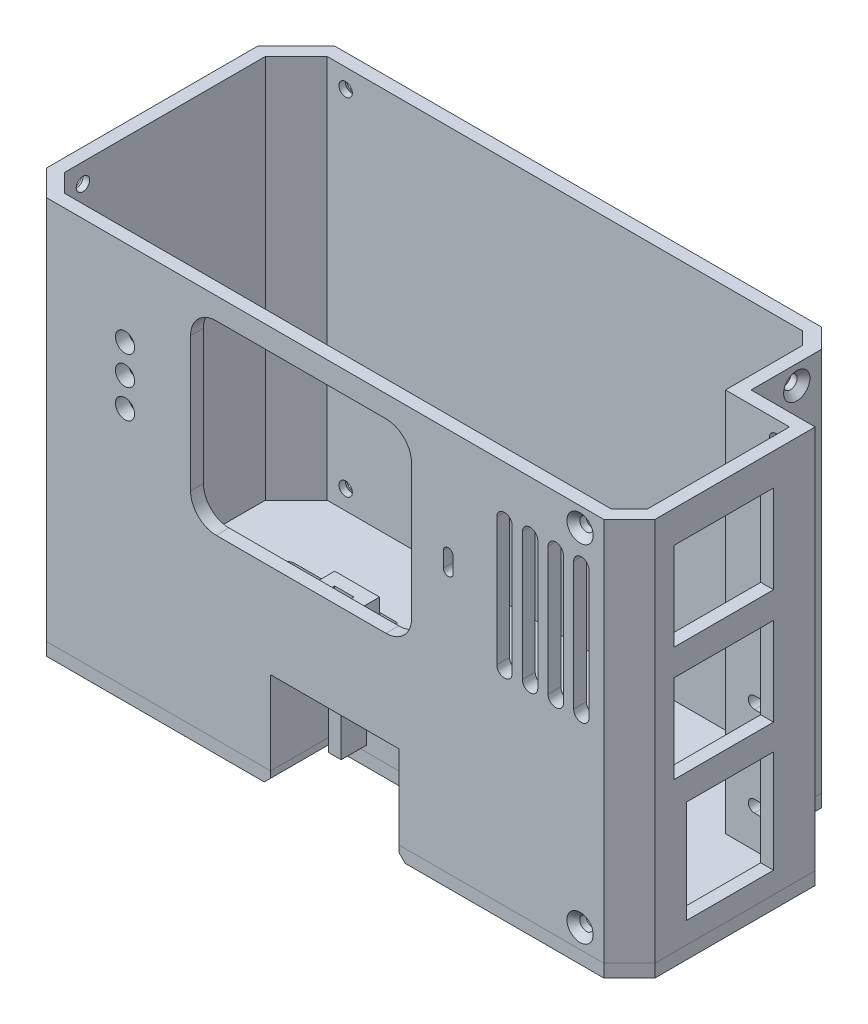
SolidWorks part; units mm, degrees
ref_plane "前视基准面" through (0, 0, 0) normal (0, 0, 1) x (1, 0, 0)
ref_plane "上视基准面" through (0, 0, 0) normal (0, 1, 0) x (1, 0, 0)
ref_plane "右视基准面" through (0, 0, 0) normal (1, 0, 0) x (0, 0, -1)
other "Configuration Table"
sketch "草图1" plane through (0, 0, 0) normal (0, 0, 1) x (1, 0, 0)
  line L1 (-105.5174, 35.9027) -> (-10.5174, 35.9027)
  line L2 (-105.5174, 35.9027) -> (-105.5174, -26.0973)
  line L3 (-105.5174, -26.0973) -> (-10.5174, -26.0973)
  line L4 (-10.5174, 35.9027) -> (-10.5174, -26.0973)
  dimension "D1" = 62
  dimension "D2" = 95
extrude "凸台-拉伸1" add sketch "草图1" along normal blind 43
sketch "草图4" plane through (0, -26.0973, 0) normal (0, -1, 0) x (1, 0, 0)
  line L0 (-10.5174, 43) -> (-10.5174, 0) construction
  line L1 (-10.5174, 14) -> (-20.5174, 14)
  line L2 (-10.5174, 14) -> (-10.5174, 0)
  line L3 (-10.5174, 0) -> (-20.5174, 0)
  line L4 (-20.5174, 14) -> (-20.5174, 0)
  line L5 (-105.5174, 0) -> (-10.5174, 0) construction
  dimension "D1" = 14
  dimension "D2" = 10
extrude "切除-拉伸3" cut sketch "草图4" against normal up to next
chamfer "倒角2" distance 6 angle 45 1 edges at (-105.5174, 4.9027, 0)
chamfer "倒角3" distance 4 angle 45 2 edges at (-105.5174, 4.9027, 43) (-10.5174, 4.9027, 43)
sketch "草图7" plane through (0, 0, 43) normal (0, 0, 1) x (1, 0, 0)
  line L0 (-101.5174, -26.0973) -> (-14.5174, -26.0973) construction
  line L1 (-46.5174, -26.0973) -> (-66.5174, -26.0973)
  line L2 (-46.5174, -26.0973) -> (-46.5174, -6.0973)
  line L3 (-46.5174, -6.0973) -> (-66.5174, -6.0973)
  line L4 (-66.5174, -26.0973) -> (-66.5174, -6.0973)
  line L6 (-10.5174, -26.0973) -> (-10.5174, 35.9027) construction
  dimension "D1" = 36
  dimension "D2" = 20
  dimension "D3" = 20
extrude "切除-拉伸5" cut sketch "草图7" against normal blind 10
shell "抽壳3" thickness 2 removed face at (-54.2952, 35.9027, 22)
sketch "草图9" plane through (0, -6.0973, 0) normal (0, -1, 0) x (1, 0, 0)
  line L0 (-44.5174, 41) -> (-68.5174, 41) construction
  line L1 (-46.5174, 41) -> (-66.5174, 41)
  line L2 (-46.5174, 41) -> (-46.5174, 33)
  line L3 (-46.5174, 33) -> (-66.5174, 33)
  line L4 (-66.5174, 41) -> (-66.5174, 33)
  line L5 (-66.5174, 33) -> (-46.5174, 33) construction
  line L8 (-66.5174, 33) -> (-66.5174, 43) construction
  line L9 (-46.5174, 33) -> (-46.5174, 43) construction
extrude "切除-拉伸6" cut sketch "草图9" against normal blind 10
sketch "草图10" plane through (0, -6.0973, 0) normal (0, -1, 0) x (1, 0, 0)
  line L4 (-66.5174, 43) -> (-66.5174, 41)
  line L5 (-66.5174, 41) -> (-46.5174, 41)
  line L6 (-46.5174, 41) -> (-46.5174, 43)
  line L7 (-46.5174, 43) -> (-66.5174, 43)
  line L8 (-66.5174, 43) -> (-66.5174, 41)
  line L9 (-66.5174, 41) -> (-46.5174, 41)
  line L10 (-46.5174, 41) -> (-46.5174, 43)
  line L11 (-46.5174, 43) -> (-66.5174, 43)
  dimension "D1" = 0
extrude "凸台-拉伸2" add sketch "草图10" along normal blind 5
sketch "草图11" plane through (0, 0, 43) normal (0, 0, 1) x (1, 0, 0)
  line L0 (-10.5174, 35.9027) -> (-10.5174, -26.0973) construction
  line L1 (-44.5174, 32.5027) -> (-79.0174, 32.5027)
  line L2 (-44.5174, 32.5027) -> (-44.5174, 3.5027)
  line L3 (-44.5174, 3.5027) -> (-79.0174, 3.5027)
  line L4 (-79.0174, 32.5027) -> (-79.0174, 3.5027)
  line L5 (-14.5174, 35.9027) -> (-101.5174, 35.9027) construction
  point P7 (0, 0)
  point P9 (-38.5314, 35.9027)
  dimension "D1" = 34.5
  dimension "D2" = 29
  dimension "D3" = 34
  dimension "D4" = 3.4
extrude "切除-拉伸7" cut sketch "草图11" against normal blind 2
fillet "圆角5" radius 4 4 edges at (-79.0174, 32.5027, 42) (-79.0174, 3.5027, 42) (-44.5174, 32.5027, 42) (-44.5174, 3.5027, 42)
sketch "草图12" plane through (0, 0, 33) normal (0, 0, 1) x (1, 0, 0)
  line L0 (-46.5174, -4.0973) -> (-66.5174, -4.0973) construction
  line L1 (-63.5174, -4.0973) -> (-49.5174, -4.0973)
  line L2 (-63.5174, -4.0973) -> (-63.5174, -23.0973)
  line L3 (-63.5174, -23.0973) -> (-49.5174, -23.0973)
  line L4 (-49.5174, -4.0973) -> (-49.5174, -23.0973)
  line L5 (-66.5174, -4.0973) -> (-66.5174, -11.0973) construction
  line L6 (-46.5174, -4.0973) -> (-46.5174, -11.0973) construction
  line L7 (-66.5174, -26.0973) -> (-46.5174, -26.0973) construction
  dimension "D1" = 3
  dimension "D2" = 3
  dimension "D3" = 3
extrude "凸台-拉伸3" add sketch "草图12" along normal blind 4
sketch "草图13" plane through (0, -4.0973, 0) normal (0, 1, 0) x (1, 0, 0)
  line L0 (-44.5174, -31) -> (-68.5174, -31) construction
  line L1 (-61.5174, -31) -> (-51.5174, -31)
  line L2 (-61.5174, -31) -> (-61.5174, -35.5752)
  line L3 (-61.5174, -35.5752) -> (-51.5174, -35.5752)
  line L4 (-51.5174, -31) -> (-51.5174, -35.5752)
  line L5 (-68.5174, -31) -> (-68.5174, -41) construction
  line L6 (-44.5174, -31) -> (-44.5174, -41) construction
  dimension "D1" = 7
  dimension "D2" = 7
extrude "切除-拉伸8" cut sketch "草图13" against normal blind 17
sketch "草图14" plane through (0, 0, 37) normal (0, 0, 1) x (1, 0, 0)
  line L0 (-63.5174, -23.0973) -> (-49.5174, -23.0973) construction
  line L1 (-61.5174, -4.0973) -> (-51.5174, -4.0973)
  line L2 (-61.5174, -4.0973) -> (-61.5174, -23.0973)
  line L3 (-61.5174, -23.0973) -> (-51.5174, -23.0973)
  line L4 (-51.5174, -4.0973) -> (-51.5174, -23.0973)
extrude "切除-拉伸9" cut sketch "草图14" against normal up to surface (4 mm away) up to face at (-56.5174, -14.3473, 33)
chamfer "倒角4" distance 1 angle 45 2 edges at (-66.5174, -26.0973, 38) (-46.5174, -26.0973, 38)
sketch "草图15" plane through (-10.5174, 0, 0) normal (1, 0, 0) x (0, 0, -1)
  line L1 (-34.05, -4.7773) -> (-20.5, -4.7773)
  line L2 (-34.05, -4.7773) -> (-34.05, -20.7773)
  line L3 (-34.05, -20.7773) -> (-20.5, -20.7773)
  line L4 (-20.5, -4.7773) -> (-20.5, -20.7773)
  line L5 (-36, 13.0027) -> (-20.5, 13.0027)
  line L6 (-36, 13.0027) -> (-36, -0.7573)
  line L7 (-36, -0.7573) -> (-20.5, -0.7573)
  line L8 (-20.5, 13.0027) -> (-20.5, -0.7573)
  line L9 (-36, 30.9027) -> (-20.5, 30.9027)
  line L10 (-36, 30.9027) -> (-36, 17.1427)
  line L11 (-36, 17.1427) -> (-20.5, 17.1427)
  line L12 (-20.5, 30.9027) -> (-20.5, 17.1427)
extrude "切除-拉伸10" cut sketch "草图15" against normal blind 2
sketch "草图16" plane through (0, 0, 43) normal (0, 0, 1) x (1, 0, 0)
  line L0 (-38.7974, 19.2027) -> (-38.7974, 16.8027) construction
  line L1 (-38.0444, 19.2027) -> (-38.0444, 16.8027)
  line L2 (-39.5504, 19.2027) -> (-39.5504, 16.8027)
  line L3 (-44.5174, 28.5027) -> (-44.5174, 7.5027) construction
  line L5 (-44.5121, 18.0027) -> (-51.3378, 18.0027) construction
  line L6 (-10.5174, -26.0973) -> (-10.5174, 35.9027) construction
  arc A0 (-38.0444, 19.2027) -> (-39.5504, 19.2027) centre (-38.7974, 19.2027) ccw
  arc A1 (-39.5504, 16.8027) -> (-38.0444, 16.8027) centre (-38.7974, 16.8027) ccw
  point P2 (-38.7974, 18.0027)
  point P14 (-44.5174, 18.0027)
  dimension "D1" = 2.4
  dimension "D2" = 28.28
extrude "切除-拉伸11" cut sketch "草图16" against normal blind 2
sketch "草图17" plane through (0, -26.0973, 0) normal (0, -1, 0) x (1, 0, 0)
  line L0 (-105.5174, 39) -> (-105.5174, 6) construction
  line L1 (-93.9174, 13.067) -> (-84.4174, 13.067)
  line L2 (-93.9174, 13.067) -> (-93.9174, 16.567)
  line L3 (-93.9174, 16.567) -> (-84.4174, 16.567)
  line L4 (-84.4174, 13.067) -> (-84.4174, 16.567)
  line L6 (-93.9174, 20.3114) -> (-84.4174, 20.3114)
  line L7 (-93.9174, 20.3114) -> (-93.9174, 23.8114)
  line L8 (-93.9174, 23.8114) -> (-84.4174, 23.8114)
  line L9 (-84.4174, 20.3114) -> (-84.4174, 23.8114)
  line L10 (-78.1448, 23.5342) -> (-71.5448, 23.5342)
  line L11 (-78.1448, 23.5342) -> (-78.1448, 20.3114)
  line L12 (-78.1448, 20.3114) -> (-71.5448, 20.3114)
  line L13 (-71.5448, 23.5342) -> (-71.5448, 20.3114)
  line L14 (-64.6448, 23.6466) -> (-58.0448, 23.6466)
  line L15 (-64.6448, 23.6466) -> (-64.6448, 20.3114)
  line L16 (-64.6448, 20.3114) -> (-58.0448, 20.3114)
  line L17 (-58.0448, 23.6466) -> (-58.0448, 20.3114)
  line L19 (-83.4263, 17.1002) -> (-76.4263, 17.1002)
  line L20 (-83.4263, 17.1002) -> (-83.4263, 13.067)
  line L21 (-83.4263, 13.067) -> (-76.4263, 13.067)
  line L22 (-76.4263, 17.1002) -> (-76.4263, 13.067)
  line L23 (-74.9763, 17.1002) -> (-67.9763, 17.1002)
  line L24 (-74.9763, 17.1002) -> (-74.9763, 13.067)
  line L25 (-74.9763, 13.067) -> (-67.9763, 13.067)
  line L26 (-67.9763, 17.1002) -> (-67.9763, 13.067)
  line L27 (-51.5174, 16.567) -> (-43.9374, 16.567)
  line L28 (-51.5174, 16.567) -> (-51.5174, 13.767)
  line L29 (-51.5174, 13.767) -> (-43.9374, 13.767)
  line L30 (-43.9374, 16.567) -> (-43.9374, 13.767)
  line L31 (-63.5659, 16.567) -> (-52.9233, 16.567)
  line L32 (-63.5659, 16.567) -> (-63.5659, 14.767)
  line L33 (-63.5659, 14.767) -> (-52.9233, 14.767)
  line L34 (-52.9233, 16.567) -> (-52.9233, 14.767)
  dimension "D1" = 11.6
  dimension "D2" = 27.3726
  dimension "D3" = 6.9
  dimension "D4" = 6.6
  dimension "D5" = 7
  dimension "D6" = 1.45
  dimension "D7" = 9.5
  dimension "D8" = 3.5
  dimension "D9" = 2.8
  dimension "D10" = 54
  dimension "D11" = 7.58
  dimension "D12" = 1.4059
  dimension "D13" = 1.8
extrude "切除-拉伸12" cut sketch "草图17" against normal blind 2
chamfer "倒角9" distance 1 angle 45 12 edges at (-78.1448, -24.0973, 21.9228) (-74.8448, -24.0973, 23.5342) (-71.5448, -24.0973, 21.9228) (-74.8448, -24.0973, 20.3114) (-61.3448, -24.0973, 23.6466) (-64.6448, -24.0973, 21.979) (-58.0448, -24.0973, 21.979) (-61.3448, -24.0973, 20.3114) (-51.5174, -24.0973, 15.167) (-47.7274, -24.0973, 16.567) (-43.9374, -24.0973, 15.167) (-47.7274, -24.0973, 13.767)
fillet "圆角2" radius 1.2 8 edges at (-93.9174, -25.0973, 16.567) (-84.4174, -25.0973, 16.567) (-84.4174, -25.0973, 13.067) (-93.9174, -25.0973, 13.067) (-93.9174, -25.0973, 20.3114) (-93.9174, -25.0973, 23.8114) (-84.4174, -25.0973, 23.8114) (-84.4174, -25.0973, 20.3114)
fillet "圆角3" radius 0.5 18 edges at (-43.9374, -25.5973, 13.767) (-51.5174, -25.5973, 13.767) (-64.6448, -25.5973, 23.6466) (-58.0448, -25.5973, 23.6466) (-71.5448, -25.5973, 23.5342) (-78.1448, -25.5973, 23.5342) (-67.9763, -25.0973, 17.1002) (-74.9763, -25.0973, 17.1002) (-76.4263, -25.0973, 17.1002) (-83.4263, -25.0973, 17.1002) (-83.4263, -25.0973, 13.067) (-74.9763, -25.0973, 13.067) (-76.4263, -25.0973, 13.067) (-67.9763, -25.0973, 13.067) (-63.5659, -25.0973, 14.767) (-63.5659, -25.0973, 16.567) (-52.9233, -25.0973, 16.567) (-52.9233, -25.0973, 14.767)
chamfer "倒角7" distance 1 angle 45 6 edges at (-51.5174, -25.5973, 16.567) (-43.9374, -25.5973, 16.567) (-58.0448, -25.5973, 20.3114) (-64.6448, -25.5973, 20.3114) (-78.1448, -25.5973, 20.3114) (-71.5448, -25.5973, 20.3114)
sketch "草图18" plane through (0, 0, 43) normal (0, 0, 1) x (1, 0, 0)
  line L1 (-79.5174, 18.0043) -> (-81.9758, 18.0043) construction
  circle A0 centre (-89.2561, 13.5043) radius 1.5
  circle A1 centre (-89.2561, 18.0043) radius 1.5
  circle A2 centre (-89.2561, 22.5043) radius 1.5
  dimension "D3" = 3
  dimension "D2" = 3
extrude "切除-拉伸13" cut sketch "草图18" against normal blind 2
sketch "草图20" plane through (0, -24.0973, 0) normal (0, 1, 0) x (1, 0, 0)
  line L1 (-83.4263, -13.567) -> (-76.9263, -13.567)
  line L2 (-83.4263, -13.567) -> (-83.4263, -16.6002)
  line L3 (-83.4263, -16.6002) -> (-76.9263, -16.6002)
  line L4 (-76.9263, -13.567) -> (-76.9263, -16.6002)
  line L5 (-74.9763, -13.567) -> (-68.4763, -13.567)
  line L6 (-74.9763, -13.567) -> (-74.9763, -16.6002)
  line L7 (-74.9763, -16.6002) -> (-68.4763, -16.6002)
  line L8 (-68.4763, -13.567) -> (-68.4763, -16.6002)
extrude "凸台-拉伸4" add sketch "草图20" against normal blind 1
sketch "草图21" plane through (0, -25.0973, 0) normal (0, -1, 0) x (1, 0, 0)
  line L0 (-76.9263, 13.567) -> (-83.4263, 13.567) construction
  line L1 (-76.9263, 16.6002) -> (-80.9263, 16.6002)
  line L2 (-76.9263, 16.6002) -> (-76.9263, 13.567)
  line L3 (-76.9263, 13.567) -> (-80.9263, 13.567)
  line L4 (-80.9263, 16.6002) -> (-80.9263, 13.567)
  line L5 (-68.4763, 13.567) -> (-74.9763, 13.567) construction
  line L6 (-68.4763, 16.6002) -> (-72.4763, 16.6002)
  line L7 (-68.4763, 16.6002) -> (-68.4763, 13.567)
  line L8 (-68.4763, 13.567) -> (-72.4763, 13.567)
  line L9 (-72.4763, 16.6002) -> (-72.4763, 13.567)
  dimension "D1" = 4
extrude "凸台-拉伸5" add sketch "草图21" along normal up to surface (1 mm away) up to face at (-61.3448, -26.0973, 22.1299)
fillet "圆角4" radius 0.5 10 edges at (-74.9763, -25.0973, 15.0836) (-83.4263, -25.0973, 15.0836) (-80.9263, -25.5973, 13.567) (-80.9263, -25.5973, 16.6002) (-72.4763, -25.5973, 16.6002) (-72.4763, -25.5973, 13.567) (-68.4763, -25.0973, 16.6002) (-68.4763, -25.0973, 13.567) (-76.9263, -25.0973, 13.567) (-76.9263, -25.0973, 16.6002)
chamfer "倒角10" distance 2 angle 45 1 edges at (-22.5174, 5.9027, 2)
chamfer "倒角11" distance 3 angle 45 1 edges at (-20.5174, 4.9027, 0)
sketch "草图26" plane through (-20.5174, 0, 0) normal (1, 0, 0) x (0, 0, -1)
  line L0 (-10, 18.9027) -> (-10, -21.0973) construction
  line L1 (-8.6566, 18.9027) -> (-8.6566, -21.0973)
  line L2 (-11.3434, 18.9027) -> (-11.3434, -21.0973)
  line L3 (-14, -26.0973) -> (-3, -26.0973) construction
  line L5 (0, 35.9027) -> (0, -26.0973) construction
  arc A0 (-8.6566, 18.9027) -> (-11.3434, 18.9027) centre (-10, 18.9027) ccw
  arc A1 (-11.3434, -21.0973) -> (-8.6566, -21.0973) centre (-10, -21.0973) ccw
  point P2 (-10, -1.0973)
  dimension "D1" = 40
  dimension "D2" = 25
  dimension "D3" = 10
extrude "切除-拉伸15" cut sketch "草图26" against normal up to next
sketch "草图27" plane through (0, 0, 43) normal (0, 0, 1) x (1, 0, 0)
  line L1 (-18.0174, 27.9027) -> (-18.0174, 7.9027) construction
  line L8 (-16.8174, 27.9027) -> (-16.8174, 7.9027)
  line L17 (-19.2174, 27.9027) -> (-19.2174, 7.9027)
  line L25 (-14.5174, 35.9027) -> (-101.5174, 35.9027) construction
  line L28 (-10.5174, 35.9027) -> (-10.5174, -26.0973) construction
  line L31 (-22.0174, 27.9027) -> (-22.0174, 7.9027) construction
  line L34 (-20.8174, 27.9027) -> (-20.8174, 7.9027)
  line L37 (-23.2174, 27.9027) -> (-23.2174, 7.9027)
  line L38 (-26.0174, 27.9027) -> (-26.0174, 7.9027) construction
  line L39 (-24.8174, 27.9027) -> (-24.8174, 7.9027)
  line L40 (-27.2174, 27.9027) -> (-27.2174, 7.9027)
  line L41 (-30.0174, 27.9027) -> (-30.0174, 7.9027) construction
  line L42 (-28.8174, 27.9027) -> (-28.8174, 7.9027)
  line L43 (-31.2174, 27.9027) -> (-31.2174, 7.9027)
  arc A44 (-16.8174, 27.9027) -> (-19.2174, 27.9027) centre (-18.0174, 27.9027) ccw
  arc A45 (-19.2174, 7.9027) -> (-16.8174, 7.9027) centre (-18.0174, 7.9027) ccw
  arc A46 (-20.8174, 27.9027) -> (-23.2174, 27.9027) centre (-22.0174, 27.9027) ccw
  arc A47 (-23.2174, 7.9027) -> (-20.8174, 7.9027) centre (-22.0174, 7.9027) ccw
  arc A48 (-24.8174, 27.9027) -> (-27.2174, 27.9027) centre (-26.0174, 27.9027) ccw
  arc A49 (-27.2174, 7.9027) -> (-24.8174, 7.9027) centre (-26.0174, 7.9027) ccw
  arc A50 (-28.8174, 27.9027) -> (-31.2174, 27.9027) centre (-30.0174, 27.9027) ccw
  arc A51 (-31.2174, 7.9027) -> (-28.8174, 7.9027) centre (-30.0174, 7.9027) ccw
  point P2 (-18.0174, 17.9027)
  point P14 (-22.0174, 17.9027)
  point P21 (-26.0174, 17.9027)
  point P28 (-30.0174, 17.9027)
  dimension "D3" = 20
  dimension "D4" = 1.2
  dimension "D1" = 8
  dimension "D2" = 7.5
  dimension "D5" = 4
sketch "草图29" plane through (-105.5174, 0, 0) normal (-1, 0, 0) x (0, 0, 1)
  line L0 (39, -26.0973) -> (6, -26.0973) construction
  circle A0 centre (35.3017, 32.9027) radius 1.05
  circle A1 centre (35.3017, -21.0973) radius 1.2021
  dimension "D1" = 2.1
  dimension "D2" = 5
extrude "切除-拉伸18" cut sketch "草图29" against normal up to next
sketch "草图30" plane through (0, 0, 0) normal (0, 0, -1) x (-1, 0, 0)
  line L0 (99.5174, -26.0973) -> (23.5174, -26.0973) construction
  circle A0 centre (95.8191, 32.9027) radius 1.05
  circle A1 centre (95.8191, -21.0973) radius 1.05
  dimension "D1" = 2.1
  dimension "D2" = 5
extrude "切除-拉伸19" cut sketch "草图30" against normal up to next
sketch "草图31" plane through (-20.5174, 0, 0) normal (1, 0, 0) x (0, 0, -1)
  line L0 (-14, -26.0973) -> (-3, -26.0973) construction
  circle A0 centre (-6.8698, 32.9027) radius 1.05
  circle A1 centre (-6.8698, -21.0973) radius 1.05
  dimension "D1" = 2.1
  dimension "D2" = 5
extrude "切除-拉伸20" cut sketch "草图31" against normal up to next
sketch "草图32" plane through (0, 0, 14) normal (0, 0, -1) x (-1, 0, 0)
  line L0 (10.5174, -26.0973) -> (20.5174, -26.0973) construction
  circle A0 centre (14.6174, 32.9027) radius 1.05
  circle A1 centre (14.6174, -21.0973) radius 1.05
  dimension "D1" = 2.1
  dimension "D2" = 5
extrude "切除-拉伸21" cut sketch "草图32" against normal up to next
sketch "草图33" plane through (0, 0, 43) normal (0, 0, 1) x (1, 0, 0)
  line L1 (-45.5174, -26.0973) -> (-14.5174, -26.0973) construction
  circle A0 centre (-18.2157, 32.9027) radius 1.05
  circle A1 centre (-18.2157, -21.0973) radius 1.05
  dimension "D1" = 2.1
  dimension "D2" = 5
extrude "切除-拉伸22" cut sketch "草图33" against normal up to next
chamfer "倒角20" distance 1 angle 45 10 edges at (-96.8691, 32.9027, 0) (-105.5174, 31.8527, 35.3017) (-17.1657, 32.9027, 43) (-15.6674, 32.9027, 14) (-20.5174, 32.9027, 5.8198) (-17.1657, -21.0973, 43) (-15.6674, -21.0973, 14) (-96.8691, -21.0973, 0) (-105.5174, -22.2995, 35.3017) (-20.5174, -21.0973, 5.8198)
sketch "草图34" plane through (0, 0, 14) normal (0, 0, -1) x (-1, 0, 0)
  line L0 (18.0174, -4.0973) -> (14.0174, -4.0973) construction
  line L1 (18.0174, -5.0973) -> (14.0174, -5.0973)
  line L2 (18.0174, -3.0973) -> (14.0174, -3.0973)
  line L3 (18.0174, -18.0973) -> (14.0174, -18.0973) construction
  line L4 (18.0174, -19.0973) -> (14.0174, -19.0973)
  line L5 (18.0174, -17.0973) -> (14.0174, -17.0973)
  line L7 (20.5174, 35.9027) -> (20.5174, -26.0973) construction
  arc A0 (18.0174, -5.0973) -> (18.0174, -3.0973) centre (18.0174, -4.0973) ccw
  arc A1 (14.0174, -3.0973) -> (14.0174, -5.0973) centre (14.0174, -4.0973) ccw
  arc A2 (18.0174, -19.0973) -> (18.0174, -17.0973) centre (18.0174, -18.0973) ccw
  arc A3 (14.0174, -17.0973) -> (14.0174, -19.0973) centre (14.0174, -18.0973) ccw
  point P3 (16.0174, -4.0973)
  point P8 (16.0174, -18.0973)
  dimension "D1" = 1
  dimension "D2" = 4
  dimension "D3" = 2.5
  dimension "D4" = 14
extrude "切除-拉伸25" cut sketch "草图34" against normal up to next (2 mm away) draft 2
extrude "切除-拉伸26" cut sketch "草图27" against normal up to next
split "分割1" bodies to split 138 resulting bodies 139 140 split by face at (-47.7274, -24.0973, 15.167)
